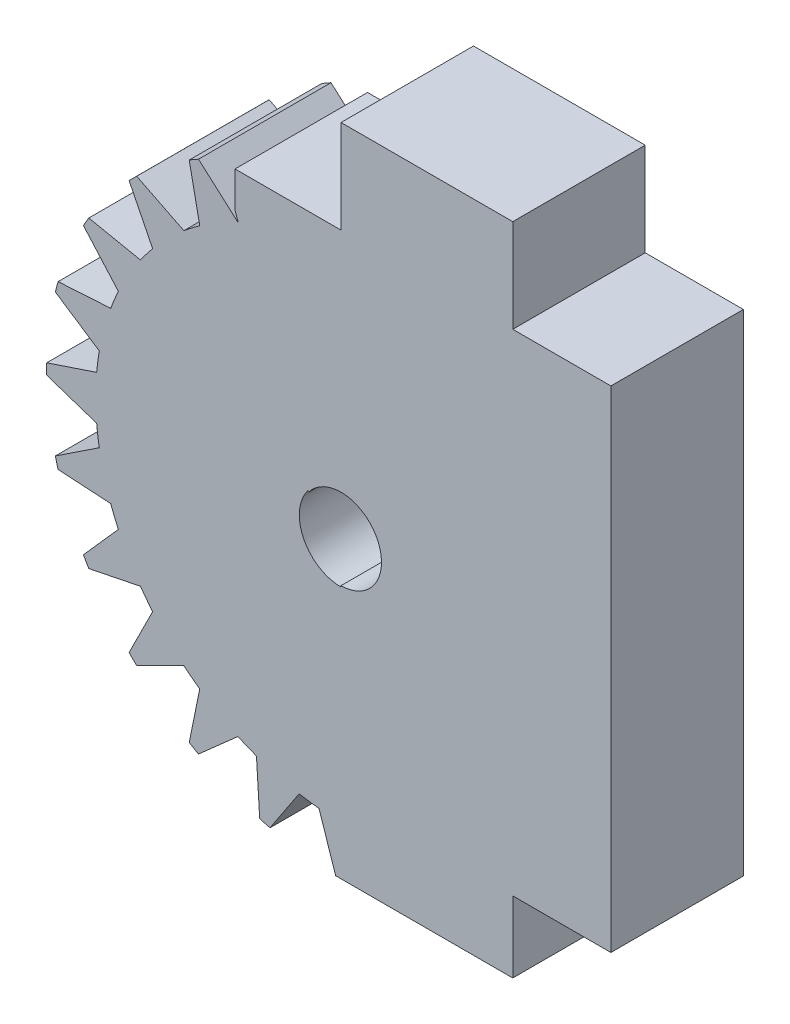
SolidWorks part; units mm, degrees
ref_plane "Front Plane" through (0, 0, 0) normal (0, 0, 1) x (1, 0, 0)
ref_plane "Top Plane" through (0, 0, 0) normal (0, 1, 0) x (1, 0, 0)
ref_plane "Right Plane" through (0, 0, 0) normal (1, 0, 0) x (0, 0, -1)
sketch "Sketch1" plane through (0, 0, 0) normal (0, 0, 1) x (1, 0, 0)
  circle A0 centre (0, 0) radius 10
  dimension "D1" = 20
extrude "Boss-Extrude1" add sketch "Sketch1" along normal blind 5.4
sketch "Sketch2" plane through (0, 0, 0) normal (0, 0, 1) x (1, 0, 0)
  line L2 (0, 12.65) -> (-0.9, 9.9594)
  line L3 (0, 12.65) -> (0.9, 9.9594)
  arc A0 (0.9, 9.9594) -> (-0.9, 9.9594) centre (0, 0) ccw
  dimension "D1" = 20
  dimension "D3" = 2.8371
  dimension "D4" = 1.8
extrude "Boss-Extrude2" add sketch "Sketch2" along normal blind 5.4
pattern_circular "CirPattern1" count 24 every 15 about axis through (0, 0, 5.4) along (0, 0, 1) of "Boss-Extrude2"
sketch "Sketch3" plane through (0, 0, 0) normal (0, 0, 1) x (1, 0, 0)
  circle A0 centre (0, 0) radius 12
  circle A1 centre (0, 0) radius 12.65
  dimension "D1" = 24
  dimension "D2" = 25.3
extrude "Cut-Extrude1" cut sketch "Sketch3" along normal blind 6
sketch "Sketch4" plane through (0, 0, 0) normal (0, 0, 1) x (1, 0, 0)
  line L0 (0, 0) -> (0, -12)
  line L1 (0, 0) -> (-20.8486, 0) construction
  line L2 (0, 0) -> (-3.8268, -9.2388) construction
  line L3 (-3.8268, 9.2388) -> (-4.5922, 11.0866)
  line L4 (-3.8268, -9.2388) -> (-4.5922, -11.0866) construction
  line L5 (0, 0) -> (-3.8268, 9.2388)
  arc A0 (0, -12) -> (-4.5922, 11.0866) centre (0, 0) ccw
  arc A2 (-4.2003, -9.0751) -> (-3.447, -9.3871) centre (0, 0) ccw construction
  dimension "D1" = 22.5
extrude "Cut-Extrude2" cut sketch "Sketch4" along normal blind 6
sketch "Sketch5" plane through (0, 0, 0) normal (0, 0, 1) x (1, 0, 0)
  circle A0 centre (0, 0) radius 1.7
  dimension "D1" = 3.4
extrude "Cut-Extrude3" cut sketch "Sketch5" along normal blind 6
sketch "Sketch6" plane through (0, 0, 0) normal (0, 0, 1) x (1, 0, 0)
  line L0 (0, 65.7933) -> (0, 76.1433) construction
  line L1 (-40.712, 32.0716) -> (40.712, 32.0716) construction
  line L2 (-4.32, 9.4388) -> (-4.32, 10.9)
  line L3 (11, 73.2433) -> (7, 73.2433) construction
  line L4 (-1.3286, 0.9785) -> (-4.32, 9.4388)
  line L5 (7, 73.2433) -> (7, 76.1433) construction
  line L6 (11, 53.2433) -> (11, 73.2433) construction
  line L7 (11, 53.2433) -> (7, 53.2433) construction
  line L8 (7, 53.2433) -> (7, 49.4433) construction
  line L9 (0, 10.9) -> (0, 14.7)
  line L10 (0, 76.1433) -> (7, 76.1433) construction
  line L11 (-4.32, 10.9) -> (0, 10.9)
  line L12 (7, 14.7) -> (0, 14.7)
  line L13 (0, -12) -> (7, -12)
  line L14 (7, 49.4433) -> (0, 49.4433) construction
  line L15 (-4.32, 53.2433) -> (0, 53.2433) construction
  line L16 (0, 53.2433) -> (0, 49.4433) construction
  line L17 (-1.3286, 63.1648) -> (-4.32, 54.7045) construction
  line L18 (-4.32, 54.7045) -> (-4.32, 53.2433) construction
  line L19 (7, 10.9) -> (7, 14.7)
  line L20 (11, 10.9) -> (7, 10.9)
  line L21 (11, 10.9) -> (11, -9.1)
  line L22 (7, -9.1) -> (7, -12)
  line L23 (11, -9.1) -> (7, -9.1)
  line L24 (0, -1.65) -> (0, -12)
  line L25 (0, 64.1433) -> (0, 0) construction
  arc A0 (-1.3286, 63.1648) -> (0, 65.7933) centre (0, 64.1433) ccw construction
  arc A1 (-1.3286, 0.9785) -> (0, -1.65) centre (0, 0) cw
  dimension "D2" = 2.9
  dimension "D6" = 7
  dimension "D3" = 1.65
  dimension "D4" = 20
  dimension "D5" = 4
  dimension "D7" = 3.8
  dimension "D8" = 7
  dimension "D9" = 4.32
  dimension "D11" = 4
extrude "Boss-Extrude3" add sketch "Sketch6" along normal blind 5.4
sketch "Sketch7" [suppressed] plane through (0, 0, 6) normal (0, 0, 1) x (1, 0, 0)
  line L0 (-0.2181, 11.998) -> (7, 12)
  line L1 (7, 12) -> (7, 9.9045)
  line L2 (7, 9.9045) -> (11, 9.9045)
  line L3 (11, 9.9045) -> (11, -10.0955)
  line L4 (11, -10.0955) -> (7, -10.0955)
  line L5 (7, -10.0955) -> (7, -13.0955)
  line L6 (7, -13.0955) -> (0, -13.0955)
  line L7 (0, -13.0955) -> (0, -10.0955)
  line L8 (0, -10.0955) -> (-3.8268, -10.0955)
  line L9 (-3.8268, -10.0955) -> (-3.8268, -9.2388)
  line L10 (-0.2181, 11.998) -> (-0.9, 9.9594)
  line L11 (-1.7084, 9.853) -> (-2.8947, 11.6456)
  line L12 (-2.8947, 11.6456) -> (-3.316, 11.5328)
  line L13 (-3.316, 11.5328) -> (-3.447, 9.3871)
  line L14 (-4.2003, 9.0751) -> (-5.8101, 10.4996)
  line L15 (-5.8101, 10.4996) -> (-6.1879, 10.2815)
  line L16 (-6.1879, 10.2815) -> (-5.7591, 8.1751)
  line L17 (-6.406, 7.6788) -> (-8.3297, 8.6381)
  line L18 (-8.3297, 8.6381) -> (-8.6381, 8.3297)
  line L19 (-8.6381, 8.3297) -> (-7.6788, 6.406)
  line L20 (-8.1751, 5.7591) -> (-10.2815, 6.1879)
  line L21 (-10.2815, 6.1879) -> (-10.4996, 5.8101)
  line L22 (-10.4996, 5.8101) -> (-9.0751, 4.2003)
  line L23 (-9.3871, 3.447) -> (-11.5328, 3.316)
  line L24 (-11.5328, 3.316) -> (-11.6456, 2.8947)
  line L25 (-11.6456, 2.8947) -> (-9.853, 1.7084)
  line L26 (-9.9594, 0.9) -> (-11.998, 0.2181)
  line L27 (-11.998, 0.2181) -> (-11.998, -0.2181)
  line L28 (-11.998, -0.2181) -> (-9.9594, -0.9)
  line L29 (-9.853, -1.7084) -> (-11.6456, -2.8947)
  line L30 (-11.6456, -2.8947) -> (-11.5328, -3.316)
  line L31 (-11.5328, -3.316) -> (-9.3871, -3.447)
  line L32 (-9.0751, -4.2003) -> (-10.4996, -5.8101)
  line L33 (-10.4996, -5.8101) -> (-10.2815, -6.1879)
  line L34 (-10.2815, -6.1879) -> (-8.1751, -5.7591)
  line L35 (-7.6788, -6.406) -> (-8.6381, -8.3297)
  line L36 (-7.6788, -6.406) -> (-8.6381, -8.3297) construction
  line L37 (-8.6381, -8.3297) -> (-8.3297, -8.6381)
  line L38 (-8.3297, -8.6381) -> (-6.406, -7.6788)
  line L39 (-5.7591, -8.1751) -> (-6.1879, -10.2815)
  line L40 (-6.1879, -10.2815) -> (-5.8101, -10.4996)
  line L41 (-5.8101, -10.4996) -> (-4.2003, -9.0751)
  circle A0 centre (0, 0) radius 1.5
  arc A1 (-0.9, 9.9594) -> (-1.7084, 9.853) centre (0, 0) ccw
  arc A2 (-3.447, 9.3871) -> (-4.2003, 9.0751) centre (0, 0) ccw
  arc A3 (-5.7591, 8.1751) -> (-6.406, 7.6788) centre (0, 0) ccw
  arc A4 (-7.6788, 6.406) -> (-8.1751, 5.7591) centre (0, 0) ccw
  arc A5 (-9.0751, 4.2003) -> (-9.3871, 3.447) centre (0, 0) ccw
  arc A6 (-9.853, 1.7084) -> (-9.9594, 0.9) centre (0, 0) ccw
  arc A7 (-4.2003, -9.0751) -> (-3.8268, -9.2388) centre (0, 0) ccw
  arc A8 (-6.406, -7.6788) -> (-5.7591, -8.1751) centre (0, 0) ccw
  arc A9 (-8.1751, -5.7591) -> (-7.6788, -6.406) centre (0, 0) ccw
  arc A10 (-9.3871, -3.447) -> (-9.0751, -4.2003) centre (0, 0) ccw
  arc A11 (-9.9594, -0.9) -> (-9.853, -1.7084) centre (0, 0) ccw
equation "\"D2@Sketch6\"= 2.1 + \"tol2@parametersSketch@prostheticParameters.SLDPRT\" * 2"
equation "\"D7@Sketch6\"= 3 + \"tol2@parametersSketch@prostheticParameters.SLDPRT\" * 2"
equation "\"D1@Boss-Extrude3\" = 5.8 - \"tol2@parametersSketch@prostheticParameters.SLDPRT\""
equation "\"D1@Boss-Extrude1\" = 5.8 - \"tol2@parametersSketch@prostheticParameters.SLDPRT\""
equation "\"D1@Boss-Extrude2\"= 5.8 - \"tol2@parametersSketch@prostheticParameters.SLDPRT\""
equation "\"D1@Sketch5\"= 3 + \"tol1@parametersSketch@prostheticParameters.SLDPRT\""
